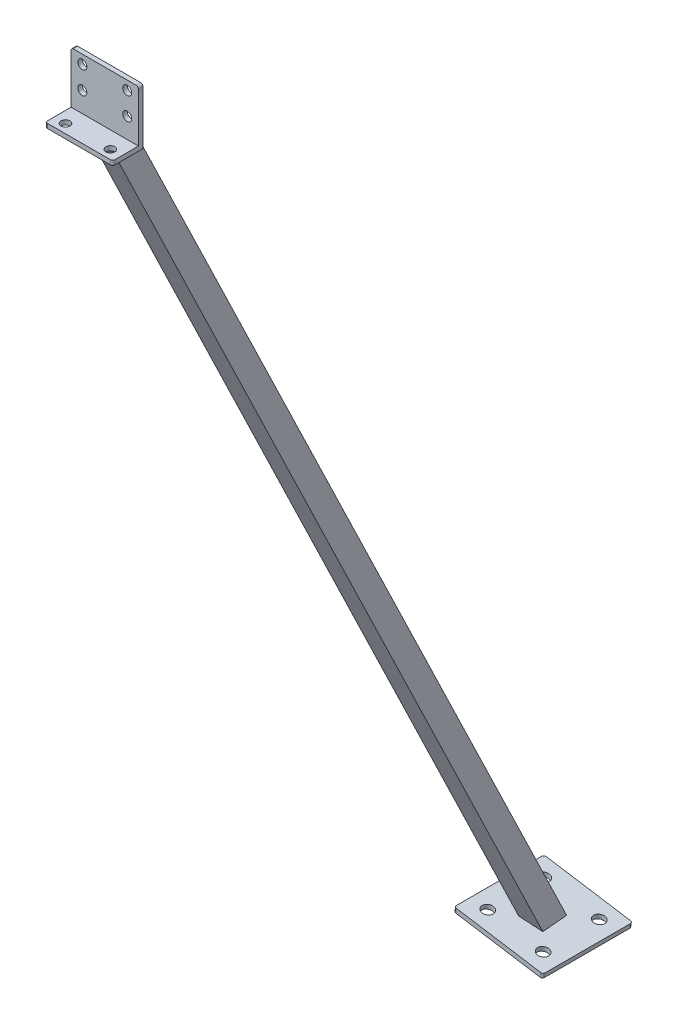
SolidWorks part; units mm, degrees
ref_plane "Front Plane" through (0, 0, 0) normal (0, 0, 1) x (1, 0, 0)
ref_plane "Top Plane" through (0, 0, 0) normal (0, 1, 0) x (1, 0, 0)
ref_plane "Right Plane" through (0, 0, 0) normal (1, 0, 0) x (0, 0, -1)
sketch "Sketch1" plane through (0, 0, 0) normal (1, 0, 0) x (0, 0, -1)
  line L0 (0, 0) -> (0, 50)
  line L1 (0, 50) -> (-4, 50)
  line L2 (-4, 50) -> (-4, 4)
  line L3 (-4, 4) -> (-27, 4)
  line L4 (-27, 4) -> (-27, 0)
  line L5 (-27, 0) -> (0, 0)
  dimension "D1" = 4
  dimension "D2" = 4
  dimension "D3" = 27
  dimension "D4" = 50
extrude "Boss-Extrude1" add sketch "Sketch1" along normal blind 60
ref_plane "Plane1" through (0, 0, 0) normal (0, -0.866, -0.5) x (-1, 0, 0)
sketch "Sketch2" plane through (0, 0, 0) normal (0, -0.866, -0.5) x (-1, 0, 0)
  line L0 (-30, 0) -> (-30, -23.3827)
  line L1 (-60, 0) -> (0, 0) construction
  line L2 (-60, -23.3827) -> (0, -23.3827) construction
ref_plane "Plane2" through (0.7342, 4.0142, 2.3176) normal (-0.1564, -0.8554, -0.4938) x (0, -0.5, 0.866)
sketch "Sketch3" plane through (0.7342, 4.0142, 2.3176) normal (-0.1564, -0.8554, -0.4938) x (0, -0.5, 0.866)
  line L0 (-9, -38.6307) -> (-9, -20.6307)
  line L1 (10, -39.6307) -> (-10, -39.6307)
  line L2 (10, -39.6307) -> (10, -19.6307)
  line L3 (10, -19.6307) -> (-10, -19.6307)
  line L4 (-10, -39.6307) -> (-10, -19.6307)
  line L5 (10, -39.6307) -> (-10, -19.6307) construction
  line L6 (10, -19.6307) -> (-10, -39.6307) construction
  line L7 (9, -20.6307) -> (-9, -20.6307)
  line L8 (9, -38.6307) -> (9, -20.6307)
  line L9 (9, -38.6307) -> (-9, -38.6307)
  point P0 (0, -29.6307)
  dimension "D1" = 20
  dimension "D2" = 20
  dimension "D3" = 1
extrude "Boss-Extrude2" add sketch "Sketch3" along normal blind 2000 and the other way blind 20
sketch "Sketch5" plane through (0, 0, 0) normal (-1, 0, 0) x (0, 0, 1)
  line L0 (4, 4) -> (4, 36.0549)
  line L1 (4, 50) -> (4, 4) construction
  line L2 (4, 36.0549) -> (38.7814, 4)
  line L3 (4, 4) -> (27, 4) construction
  line L4 (38.7814, 4) -> (4, 4)
extrude "Cut-Extrude1" cut sketch "Sketch5" against normal blind 60
ref_plane "Plane3" through (-155.5473, -982.0868, 0) normal (0.1564, 0.9877, 0) x (0.9877, -0.1564, 0)
sketch "Sketch7" plane through (-155.5473, -982.0868, 0) normal (0.1564, 0.9877, 0) x (0.9877, -0.1564, 0)
  line L0 (19.2115, 0) -> (-22.5192, 995.5664) construction
  line L1 (-22.5192, 995.5664) -> (-2.5847, 997.1308) construction
  line L3 (45.477, 526.4414) -> (-34.523, 526.4414)
  line L4 (45.477, 526.4414) -> (45.477, 606.4414)
  line L5 (45.477, 606.4414) -> (-34.523, 606.4414)
  line L6 (-34.523, 526.4414) -> (-34.523, 606.4414)
  line L7 (45.477, 526.4414) -> (-34.523, 606.4414) construction
  line L8 (45.477, 606.4414) -> (-34.523, 526.4414) construction
  point P0 (5.477, 566.4414)
  point P5 (5.477, 566.4414)
  dimension "D1" = 10
  dimension "D2" = 430
  dimension "D3" = 80
  dimension "D4" = 80
extrude "Boss-Extrude3" add sketch "Sketch7" along normal blind 4
sketch "Sketch8" plane through (-155.5473, -982.0868, 0) normal (-0.1564, -0.9877, 0) x (0.9877, -0.1564, 0)
  line L1 (-50.2657, -545.5822) -> (58.9366, -545.5822)
  line L2 (-50.2657, -545.5822) -> (-50.2657, -1028.5491)
  line L3 (-50.2657, -1028.5491) -> (58.9366, -1028.5491)
  line L4 (58.9366, -545.5822) -> (58.9366, -1028.5491)
extrude "Cut-Extrude3" cut sketch "Sketch8" along normal blind 1000
sketch "Sketch9" plane through (0, 0, 0) normal (0, 0, -1) x (-1, 0, 0)
  circle A0 centre (-50, 22) radius 4 construction
  circle A1 centre (-10, 22) radius 4 construction
  circle A2 centre (-10, 42) radius 4 construction
  circle A3 centre (-50, 42) radius 4 construction
  circle A4 centre (-50, 22) radius 4
  circle A5 centre (-10, 22) radius 4
  circle A6 centre (-10, 42) radius 4
  circle A7 centre (-50, 42) radius 4
extrude "Cut-Extrude4" cut sketch "Sketch9" against normal up to next
sketch "Sketch10" plane through (0, 0, 0) normal (0, -1, 0) x (1, 0, 0)
  circle A0 centre (50, 19) radius 4 construction
  circle A1 centre (10, 19) radius 4 construction
  circle A2 centre (50, 19) radius 4
  circle A3 centre (10, 19) radius 4
extrude "Cut-Extrude5" cut sketch "Sketch10" against normal up to next
sketch "Sketch11" plane through (-155.5473, -982.0868, 0) normal (-0.1564, -0.9877, 0) x (0.9877, -0.1564, 0)
  line L0 (-34.523, -526.4414) -> (45.477, -526.4414) construction
  line L1 (-34.523, -606.4414) -> (-34.523, -526.4414) construction
  circle A0 centre (-19.523, -541.4414) radius 5
  circle A1 centre (30.477, -541.4414) radius 5
  circle A2 centre (30.477, -591.4414) radius 5
  circle A3 centre (-19.523, -591.4414) radius 5
  dimension "D1" = 10
  dimension "D4" = 2
  dimension "D2" = 15
  dimension "D3" = 15
  dimension "D5" = 2
extrude "Cut-Extrude6" cut sketch "Sketch11" against normal up to next
fillet "Fillet1" radius 2 4 edges at (60, 2, 27) (0, 2, 27) (0, 50, 2) (60, 50, 2)
fillet "Fillet2" radius 2 4 edges at (-110.3173, -987.2256, -606.4414) (-189.3323, -974.7108, -606.4414) (-110.3173, -987.2256, -526.4414) (-189.3323, -974.7108, -526.4414)
